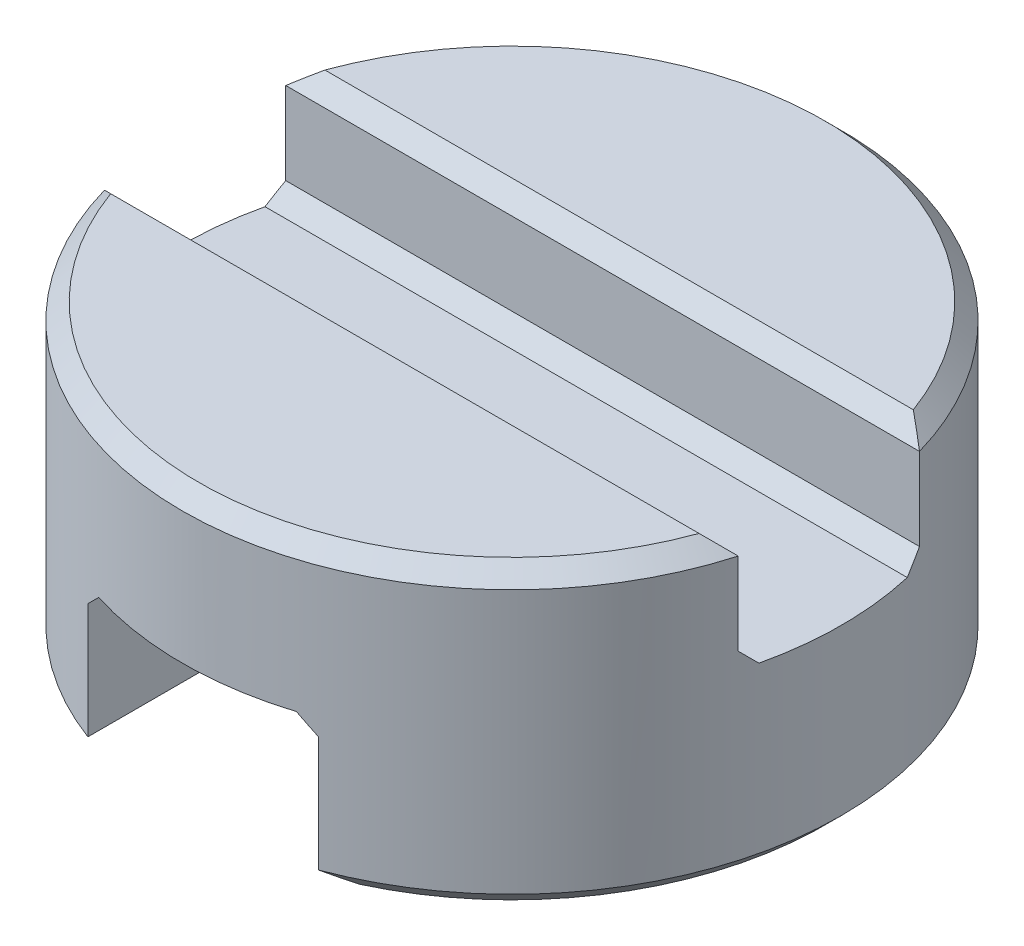
SolidWorks part; units mm, degrees
ref_plane "Спереди" through (0, 0, 0) normal (0, 0, 1) x (1, 0, 0)
ref_plane "Сверху" through (0, 0, 0) normal (0, 1, 0) x (1, 0, 0)
ref_plane "Справа" through (0, 0, 0) normal (1, 0, 0) x (0, 0, -1)
sketch "Эскиз1" plane through (0, 0, 0) normal (0, 1, 0) x (1, 0, 0)
  circle A0 centre (0, 0) radius 10
  dimension "D1" = 20
extrude "Бобышка-Вытянуть1" add sketch "Эскиз1" along normal blind 9
sketch "Эскиз2" plane through (0, 0, 0) normal (0, -1, 0) x (1, 0, 0)
  line L1 (3.5, 10) -> (-3.5, 10)
  line L2 (3.5, 10) -> (3.5, -10)
  line L3 (3.5, -10) -> (-3.5, -10)
  line L4 (-3.5, 10) -> (-3.5, -10)
  line L5 (3.5, 10) -> (-3.5, -10) construction
  line L6 (3.5, -10) -> (-3.5, 10) construction
  circle A0 centre (0, 0) radius 10 construction
  point P0 (0, 0)
  dimension "D1" = 7
extrude "Вырез-Вытянуть1" cut sketch "Эскиз2" against normal blind 4.5
chamfer "Фаска1" distance 0.5 angle 45 6 edges at (-10, 0, 0) (-3.5, 0, 0) (10, 0, 0) (3.5, 0, 0) (-3.5, 4.5, 0) (3.5, 4.5, 0)
sketch "Эскиз3" plane through (0, 9, 0) normal (0, 1, 0) x (1, 0, 0)
  line L1 (11, 2.75) -> (-11, 2.75)
  line L2 (11, 2.75) -> (11, -2.75)
  line L3 (11, -2.75) -> (-11, -2.75)
  line L4 (-11, 2.75) -> (-11, -2.75)
  line L5 (11, 2.75) -> (-11, -2.75) construction
  line L6 (11, -2.75) -> (-11, 2.75) construction
  point P0 (0, 0)
  dimension "D1" = 22
  dimension "D2" = 5.5
extrude "Вырез-Вытянуть2" cut sketch "Эскиз3" against normal blind 3.5
chamfer "Фаска2" distance 0.5 angle 45 6 edges at (0, 9, 10) (0, 9, 2.75) (0, 9, -10) (0, 9, -2.75) (0, 5.5, 2.75) (0, 5.5, -2.75)
equation "\"D1@Бобышка-Вытянуть1\"=5.50мм+3.5"
